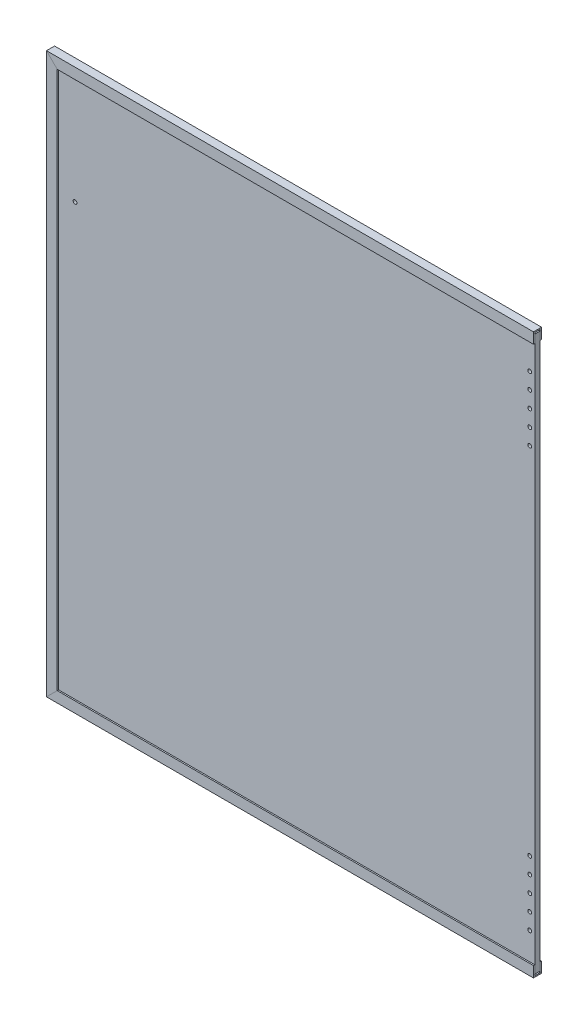
SolidWorks part; units mm, degrees
material "Plywood"
ref_plane "Front Plane" through (0, 0, 0) normal (0, 0, 1) x (1, 0, 0)
ref_plane "Top Plane" through (0, 0, 0) normal (0, 1, 0) x (1, 0, 0)
ref_plane "Right Plane" through (0, 0, 0) normal (1, 0, 0) x (0, 0, -1)
sketch "Shelf opening" plane through (0, 0, 0) normal (0, 0, 1) x (1, 0, 0)
  line L1 (0, 0) -> (577.85, 0)
  line L2 (0, 0) -> (0, 635)
  line L3 (0, 635) -> (577.85, 635)
  line L4 (577.85, 0) -> (577.85, 635)
  dimension "D1" = 577.85
  dimension "D2" = 635
sketch "Sketch2" plane through (0, 0, 0) normal (0, 0, 1) x (1, 0, 0)
  line L0 (577.85, 0) -> (577.85, 635) construction
  line L1 (3.175, 647.7) -> (577.85, 647.7)
  line L2 (3.175, 647.7) -> (3.175, -12.7)
  line L3 (3.175, -12.7) -> (577.85, -12.7)
  line L4 (577.85, 647.7) -> (577.85, -12.7)
  line L5 (0, 635) -> (577.85, 635) construction
  line L6 (0, 0) -> (0, 635) construction
  line L7 (0, 0) -> (577.85, 0) construction
  dimension "D1" = 12.7
  dimension "D2" = 3.175
  dimension "D3" = 12.7
extrude "Frame outer dimensions" add sketch "Sketch2" along normal mid plane 9.525
sketch "Sketch3" plane through (0, 0, 4.7625) normal (0, 0, 1) x (1, 0, 0)
  line L0 (577.85, -12.7) -> (577.85, 647.7) construction
  line L1 (577.85, 635) -> (15.875, 635)
  line L2 (577.85, 635) -> (577.85, 0)
  line L3 (577.85, 0) -> (15.875, 0)
  line L4 (15.875, 635) -> (15.875, 0)
  line L5 (577.85, 647.7) -> (3.175, 647.7) construction
  line L6 (3.175, 647.7) -> (3.175, -12.7) construction
  line L7 (3.175, -12.7) -> (577.85, -12.7) construction
  dimension "D1" = 12.7
  dimension "D2" = 12.7
  dimension "D3" = 12.7
extrude "Frame inner dimensions" cut sketch "Sketch3" against normal through all
sketch "Sketch4" plane through (0, 0, 0) normal (0, 0, 1) x (1, 0, 0)
  line L0 (577.85, 635) -> (577.85, 647.7) construction
  line L1 (577.85, 646.1125) -> (4.7625, 646.1125)
  line L2 (577.85, 646.1125) -> (577.85, -11.1125)
  line L3 (577.85, -11.1125) -> (4.7625, -11.1125)
  line L4 (4.7625, 646.1125) -> (4.7625, -11.1125)
  line L5 (577.85, 647.7) -> (3.175, 647.7) construction
  line L6 (3.175, 647.7) -> (3.175, -12.7) construction
  line L7 (3.175, -12.7) -> (577.85, -12.7) construction
  dimension "D1" = 1.5875
  dimension "D2" = 1.5875
  dimension "D3" = 1.5875
extrude "Frame profile" cut sketch "Sketch4" along normal offset from surface 1.5875 and the other way offset from surface 1.5875 up to face at (293.6875, 317.5, 4.7625) other way up to face at (293.6875, 317.5, -4.7625)
sketch "Frame sections" plane through (0, 0, 4.7625) normal (0, 0, 1) x (1, 0, 0)
  line L0 (3.175, 647.7) -> (15.875, 635)
  line L1 (3.175, -12.7) -> (15.875, 0)
split "Frame section split" trim tools "Frame sections" bodies to split 103 resulting bodies 105 106 107
sketch "Sketch5" plane through (0, 0, 0) normal (0, 0, 1) x (1, 0, 0)
  line L0 (577.85, 635) -> (577.85, 647.7) construction
  line L1 (577.85, 644.525) -> (6.35, 644.525)
  line L2 (577.85, 644.525) -> (577.85, -9.525)
  line L3 (577.85, -9.525) -> (6.35, -9.525)
  line L4 (6.35, 644.525) -> (6.35, -9.525)
  line L5 (4.7625, 646.1125) -> (577.85, 646.1125) construction
  line L6 (4.7625, -11.1125) -> (4.7625, 646.1125) construction
  line L7 (577.85, -11.1125) -> (4.7625, -11.1125) construction
  dimension "D1" = 1.5875
  dimension "D2" = 1.5875
  dimension "D3" = 1.5875
  dimension "D4" = 571.5
  dimension "D5" = 654.05
extrude "Door panel" add sketch "Sketch5" along normal mid plane 5.588 separate body
sketch "Hinge positions" plane through (0, 0, 2.794) normal (0, 0, 1) x (1, 0, 0)
  line L0 (577.85, -9.525) -> (577.85, 644.525) construction
  line L1 (577.85, 612.775) -> (565.15, 612.775)
  line L2 (577.85, 612.775) -> (577.85, 517.525)
  line L3 (577.85, 517.525) -> (565.15, 517.525)
  line L4 (565.15, 612.775) -> (565.15, 517.525)
  line L5 (565.15, 117.475) -> (577.85, 117.475)
  line L6 (565.15, 117.475) -> (565.15, 22.225)
  line L7 (565.15, 22.225) -> (577.85, 22.225)
  line L8 (577.85, 117.475) -> (577.85, 22.225)
  line L10 (0, 0) -> (577.85, 0) construction
  line L11 (0, 635) -> (577.85, 635) construction
  dimension "D1" = 95.25
  dimension "D2" = 12.7
  dimension "D3" = 22.225
  dimension "D4" = 22.225
  dimension "D5" = 495.3
sketch "Sketch8" plane through (0, 0, 2.794) normal (0, 0, 1) x (1, 0, 0)
  line L0 (565.15, 69.85) -> (577.85, 69.85) construction
  line L2 (565.15, 117.475) -> (565.15, 22.225) construction
  line L3 (577.85, 117.475) -> (577.85, 22.225) construction
  line L4 (565.15, 565.15) -> (577.85, 565.15) construction
  line L6 (565.15, 612.775) -> (565.15, 517.525) construction
  line L7 (577.85, 612.775) -> (577.85, 517.525) construction
  point P0 (571.5, 31.75)
  point P11 (571.5, 50.8)
  point P12 (571.5, 69.85)
  point P13 (571.5, 88.9)
  point P14 (571.5, 107.95)
  point P15 (571.5, 546.1)
  point P16 (571.5, 565.15)
  point P17 (571.5, 584.2)
  point P18 (571.5, 603.25)
  point P19 (571.5, 527.05)
  dimension "D3" = 19.05
  dimension "D1" = 5
  dimension "D2" = 2
hole_wizard "#8 Clearance Hole1" positions "Sketch8" profile "Sketch9" hole size "#8" standard "ANSI Inch" end condition through all
sketch "Sketch9" plane through (571.5, 31.75, 2.794) normal (1, 0, 0) x (0, -1, 0)
  line L0 (0, 0) -> (0, 7.5565)
  line L1 (0, 7.5565) -> (2.2479, 7.5565)
  line L2 (2.2479, 7.5565) -> (2.2479, 0)
  line L5 (2.2479, 0) -> (0, 0)
  line L11 (0, -6.35) -> (0, 107.95) construction
  dimension "Thru Hole Dia." = 4.4958
  dimension "Thru Hole Depth" = 7.5565
sketch "Handle positions" plane through (0, 0, 2.794) normal (0, 0, 1) x (1, 0, 0)
  line L1 (6.35, 644.525) -> (44.45, 644.525)
  line L2 (6.35, 644.525) -> (6.35, 495.3)
  line L3 (6.35, 495.3) -> (44.45, 495.3)
  line L4 (44.45, 644.525) -> (44.45, 495.3)
  line L5 (6.35, 644.525) -> (6.35, -9.525) construction
  line L6 (577.85, 644.525) -> (6.35, 644.525) construction
  dimension "D1" = 149.225
  dimension "D2" = 38.1
sketch "Sketch11" plane through (0, 0, 2.794) normal (0, 0, 1) x (1, 0, 0)
  line L0 (34.925, 508) -> (34.925, 635) construction
  line L2 (6.35, 644.525) -> (6.35, 495.3) construction
  line L3 (6.35, 644.525) -> (44.45, 644.525) construction
  point P0 (34.925, 635)
  point P2 (34.925, 508)
  point P8 (70.9463, 612.5255)
  point P9 (26.6232, 527.5729)
  dimension "D1" = 28.575
  dimension "D2" = 9.525
  dimension "D3" = 136.525
hole_wizard "#8 Clearance Hole2" positions "Sketch11" profile "Sketch12" hole size "#8" standard "ANSI Inch" end condition through all
sketch "Sketch12" plane through (34.925, 635, 2.794) normal (1, 0, 0) x (0, -1, 0)
  line L0 (0, 0) -> (0, 7.5565)
  line L1 (0, 7.5565) -> (2.2479, 7.5565)
  line L2 (2.2479, 7.5565) -> (2.2479, 0)
  line L5 (2.2479, 0) -> (0, 0)
  line L11 (0, -6.35) -> (0, 107.95) construction
  dimension "Thru Hole Dia." = 4.4958
  dimension "Thru Hole Depth" = 7.5565
mirror "Mirror1" about plane through (0, 0, 0) normal (1, 0, 0) of bodies 105 106 107 114 108
delete or keep bodies "Body-Delete/Keep 1" type keep bodies bodies 105 106 107 114
delete or keep bodies "Body-Delete/Keep 2" [suppressed] type keep bodies bodies 109 110 111 112
